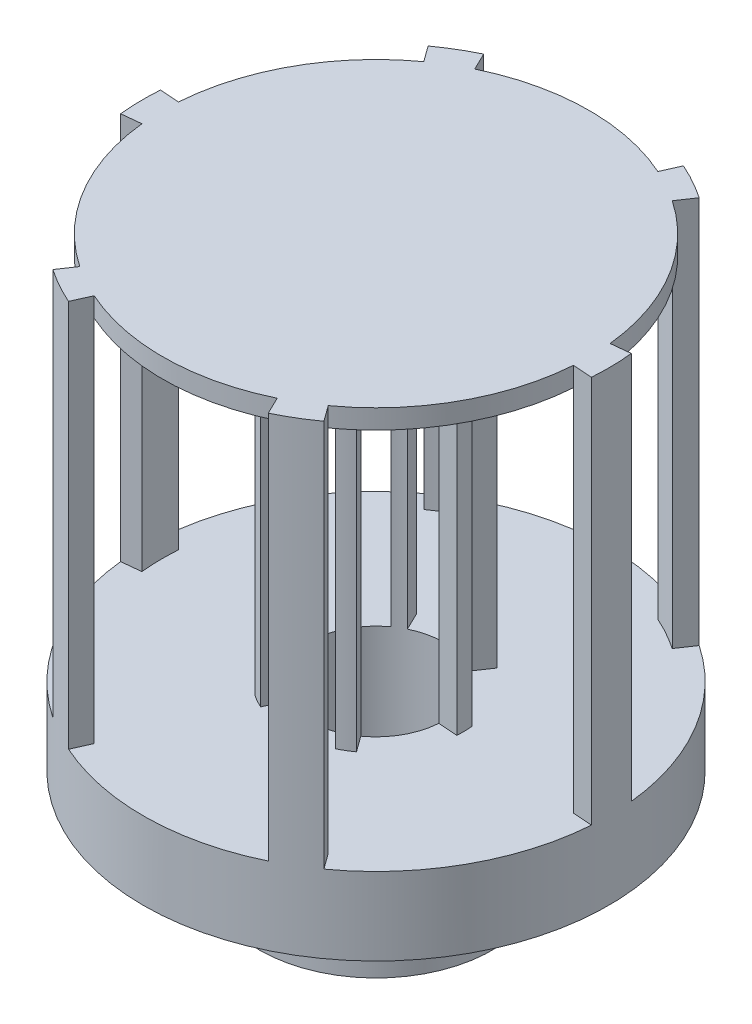
SolidWorks part; units mm, degrees
material "ABS"
ref_plane "Front" through (0, 0, 0) normal (0, 0, 1) x (1, 0, 0)
ref_plane "Top" through (0, 0, 0) normal (0, 1, 0) x (1, 0, 0)
ref_plane "Right" through (0, 0, 0) normal (1, 0, 0) x (0, 0, -1)
sketch "Sketch1" plane through (0, 0, 0) normal (0, 1, 0) x (1, 0, 0)
  circle A0 centre (0, 0) radius 6
extrude "Boss-Extrude1" add sketch "Sketch1" along normal blind 6
sketch "Sketch2" plane through (0, 6, 0) normal (0, 1, 0) x (1, 0, 0)
  circle A0 centre (0, 0) radius 12
extrude "Boss-Extrude2" add sketch "Sketch2" along normal blind 3
sketch "Sketch5" plane through (0, 6, 0) normal (0, -1, 0) x (1, 0, 0)
  circle A0 centre (0, 0) radius 12
  circle A1 centre (0, 0) radius 11
extrude "Boss-Extrude3" add sketch "Sketch5" along normal blind 1
sketch "Sketch6" plane through (0, 9, 0) normal (0, 1, 0) x (1, 0, 0)
  circle A0 centre (0, 0) radius 12
  circle A1 centre (0, 0) radius 11
extrude "Boss-Extrude4" add sketch "Sketch6" along normal blind 20
sketch "Sketch7" plane through (0, 29, 0) normal (0, 1, 0) x (1, 0, 0)
  line L3 (-5.2401, 10.7955) -> (-4.8034, 9.8958)
  line L5 (4.9016, 10.9533) -> (4.4931, 10.0405)
  arc A0 (-5.2401, 10.7955) -> (4.9016, 10.9533) centre (0, 0) cw
  circle A1 centre (0, 0) radius 11 construction
  circle A2 centre (0, 0) radius 11 construction
  arc A3 (4.4931, 10.0405) -> (-4.8034, 9.8958) centre (0, 0) ccw
extrude "Cut-Extrude1" cut sketch "Sketch7" against normal blind 20
pattern_circular "CirPattern1" count 6 over 360 about axis through (0, 0, 0) along (0, 1, 0) of "Cut-Extrude1"
sketch "Sketch8" plane through (0, 0, 0) normal (0, -1, 0) x (1, 0, 0)
  circle A0 centre (0, 0) radius 3.5
extrude "Cut-Extrude2" cut sketch "Sketch8" against normal blind 9
sketch "Sketch9" plane through (0, 9, 0) normal (0, 1, 0) x (1, 0, 0)
  line L2 (-2.6381, 3.6456) -> (-2.0519, 2.8354)
  line L3 (-1.965, 4.0483) -> (-1.5283, 3.1487)
  arc A0 (-2.0519, 2.8354) -> (-1.5283, 3.1487) centre (0, 0) cw
  circle A1 centre (0, 0) radius 3.5 construction
  arc A2 (-2.6381, 3.6456) -> (-1.965, 4.0483) centre (0, 0) cw
extrude "Boss-Extrude5" add sketch "Sketch9" along normal blind 20
pattern_circular "CirPattern2" count 6 over 360 about axis through (0, 9, 0) along (0, -1, 0) of "Boss-Extrude5"
ref_plane "Plane1" through (0, 29, 0) normal (0, 1, 0) x (1, 0, 0)
sketch "Sketch12" plane through (0, 29, 0) normal (0, 1, 0) x (1, 0, 0)
  circle A0 centre (0, 0) radius 11
extrude "Boss-Extrude6" add sketch "Sketch12" against normal blind 1
